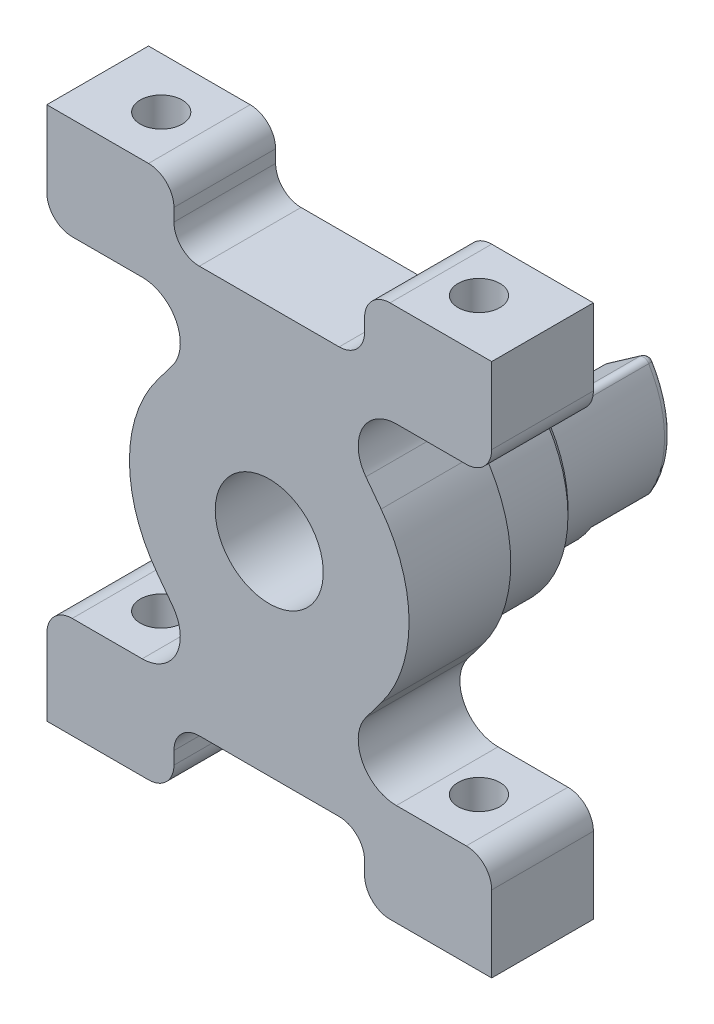
SolidWorks part; units mm, degrees
material "6061 合金"
ref_plane "前视基准面" through (0, 0, 0) normal (0, 0, 1) x (1, 0, 0)
ref_plane "上视基准面" through (0, 0, 0) normal (0, 1, 0) x (1, 0, 0)
ref_plane "右视基准面" through (0, 0, 0) normal (1, 0, 0) x (0, 0, -1)
sketch "草图1" plane through (0, 0, 0) normal (0, 0, 1) x (1, 0, 0)
  line L1 (-17.5, 21) -> (17.5, 21)
  line L2 (-17.5, 21) -> (-17.5, -21)
  line L3 (-17.5, -21) -> (17.5, -21)
  line L4 (17.5, 21) -> (17.5, -21)
  line L5 (-17.5, 21) -> (17.5, -21) construction
  line L6 (-17.5, -21) -> (17.5, 21) construction
  point P0 (0, 0)
  dimension "D1" = 35
  dimension "D2" = 42
extrude "凸台-拉伸1" add sketch "草图1" along normal mid plane 8
sketch "草图2" plane through (0, 21, 0) normal (0, 1, 0) x (1, 0, 0)
  line L0 (-12.5, 0) -> (12.5, 0) construction
  point P3 (0, 0)
  dimension "D1" = 25
sketch "草图5" plane through (0, 0, -4) normal (0, 0, -1) x (-1, 0, 0)
  circle A0 centre (0, 0) radius 8.5
  dimension "D1" = 17
extrude "凸台-拉伸2" add sketch "草图5" along normal blind 10.1
sketch "草图6" plane through (0, 0, 0) normal (0, 1, 0) x (1, 0, 0)
  line L0 (8.5, 4) -> (8.5, 14.1) construction
  line L1 (8.5, 10) -> (10, 10)
  line L2 (8.5, 10) -> (8.5, 4)
  line L3 (8.5, 4) -> (10, 4)
  line L4 (10, 10) -> (10, 4)
  line L5 (17.5, 4) -> (-17.5, 4) construction
  line L6 (0, 0) -> (0, 4) construction
  dimension "D1" = 6
  dimension "D3" = 10
revolve "旋转1" add sketch "草图6" angle 360 about L6
chamfer "倒角1" distance 0.5 angle 45 1 edges at (10, 0, -10)
sketch "草图7" plane through (0, 0, -14.1) normal (0, 0, -1) x (-1, 0, 0)
  circle A0 centre (0, 0) radius 6.5 construction
  dimension "D1" = 13
hole_wizard "M3 螺纹孔1" positions "草图8" profile "草图9" tap size "M3" standard "ISO"
sketch "草图8" plane through (0, 0, -14.1) normal (0, 0, -1) x (-1, 0, 0)
  circle A0 centre (0, 0) radius 6.5 construction
  point P0 (0, 6.5)
  point P6 (0, -6.5)
sketch "草图9" plane through (0, 6.5, -14.1) normal (1, 0, 0) x (0, 1, 0)
  line L0 (0, 0) -> (0, 10.7511)
  line L1 (0, 10.7511) -> (1.25, 10)
  line L2 (1.25, 10) -> (1.25, 0)
  line L5 (1.25, 0) -> (0, 0)
  line L10 (0, 10.7511) -> (-1.25, 10) construction
  line L11 (0, -6.35) -> (0, 107.95) construction
  dimension "螺纹孔钻头直径" = 2.5
  dimension "螺纹孔钻头深度" = 10
  dimension "导头角度" = 118
cosmetic thread "孔螺蚊线4" parameters "D1"=6, "D2"=3
cosmetic thread "孔螺蚊线6" parameters "D1"=6, "D2"=3
sketch "草图10" plane through (0, 0, -14.1) normal (0, 0, -1) x (-1, 0, 0)
  circle A0 centre (0, 0) radius 4.25
  dimension "D1" = 8.5
extrude "切除-拉伸1" cut sketch "草图10" against normal through all
sketch "草图12" plane through (0, 0, -4) normal (0, 0, -1) x (-1, 0, 0)
  line L0 (17.5, 0) -> (21, 0)
  line L1 (-17.5, 21) -> (17.5, 21)
  line L2 (-17.5, 21) -> (-17.5, -21)
  line L3 (-17.5, -21) -> (17.5, -21)
  line L4 (17.5, 21) -> (17.5, -21)
  line L5 (-17.5, 21) -> (17.5, -21) construction
  line L6 (-17.5, -21) -> (17.5, 21) construction
  line L7 (-17.5, 0) -> (-21, 0)
  line L8 (-17.5, 11.6082) -> (-13.0958, 11.6082)
  line L9 (13.0958, 11.6082) -> (17.5, 11.6082)
  line L10 (17.5, -11.6082) -> (13.0958, -11.6082)
  line L11 (-13.0958, -11.6082) -> (-17.5, -11.6082)
  circle A0 centre (0, 0) radius 17.5
  circle A1 centre (0, 0) radius 21
  dimension "D1" = 42
  dimension "D2" = 35
sketch "草图13" plane through (0, 0, -14.1) normal (0, 0, -1) x (-1, 0, 0)
  line L0 (-8.5, 0) -> (8.5, 0) construction
  line L1 (6.9628, 4.8754) -> (0, 0)
  line L2 (0, 0) -> (6.9628, -4.8754)
  circle A0 centre (0, 0) radius 4.25
  circle A1 centre (0, 0) radius 8.5
  circle A3 centre (0, 0) radius 8.5 construction
  circle M6 centre (0, 0) radius 4.25
  circle M9 centre (0, 0) radius 8.5
  dimension "D1" = 8.5
  dimension "D2" = 35
  dimension "D3" = 35
extrude "凸台-拉伸3" add sketch "草图13" along normal blind 5 contours L0 A1 L1 M6 | L0 A0 L2 M9 region at (-6.2076, 1.9572, -14.1) region at (-6.2076, -1.9572, -14.1)
mirror "镜向1" about plane through (0, 0, 0) normal (1, 0, 0) of "凸台-拉伸3"
fillet "圆角1" radius 0.5 16 edges at (-5.2221, 3.6565, -19.1) (-5.2221, -3.6565, -19.1) (-4.25, 0, -19.1) (-8.5, 0, -19.1) (5.2221, -3.6565, -19.1) (5.2221, 3.6565, -19.1) (8.5, 0, -19.1) (4.25, 0, -19.1) (3.4814, 2.4377, -16.6) (6.9628, 4.8754, -16.6) (6.9628, -4.8754, -16.6) (3.4814, -2.4377, -16.6) (-3.4814, 2.4377, -16.6) (-6.9628, 4.8754, -16.6) (-6.9628, -4.8754, -16.6) (-3.4814, -2.4377, -16.6)
sketch "草图14" plane through (0, 0, -4) normal (0, 0, -1) x (-1, 0, 0)
  line L4 (-17.5, 21) -> (-17.5, -21)
  line L5 (-17.5, -21) -> (17.5, -21)
  line L6 (17.5, -21) -> (17.5, 21)
  line L7 (17.5, 21) -> (-17.5, 21)
  line L8 (-17.5, 21) -> (-17.5, -21)
  line L9 (-17.5, -21) -> (17.5, -21)
  line L10 (17.5, -21) -> (17.5, 21)
  line L11 (17.5, 21) -> (-17.5, 21)
  line L30 (9.5, -21) -> (15.5, -21)
  line L31 (7.5, -18) -> (7.5, -19)
  line L32 (-5.5, -16) -> (5.5, -16)
  line L33 (-7.5, -19) -> (-7.5, -18)
  line L34 (-15.5, -21) -> (-9.5, -21)
  line L35 (-17.5, -15) -> (-17.5, -19)
  line L36 (-10, -13) -> (-15.5, -13)
  line L37 (-8.8, -6.6) -> (-7.6, -8.2)
  line L38 (7.6, -8.2) -> (8.8, -6.6)
  line L39 (15.5, -13) -> (10, -13)
  line L40 (17.5, -19) -> (17.5, -15)
  line L41 (-17.5, -21) -> (-17.5, 21) construction
  line L42 (17.5, -21) -> (-17.5, -21) construction
  line L52 (-9.5, 21) -> (-15.5, 21)
  line L53 (-7.5, 18) -> (-7.5, 19)
  line L54 (5.5, 16) -> (-5.5, 16)
  line L55 (7.5, 19) -> (7.5, 18)
  line L56 (15.5, 21) -> (9.5, 21)
  line L57 (17.5, 15) -> (17.5, 19)
  line L58 (10, 13) -> (15.5, 13)
  line L59 (8.8, 6.6) -> (7.6, 8.2)
  line L60 (-7.6, 8.2) -> (-8.8, 6.6)
  line L61 (-15.5, 13) -> (-10, 13)
  line L62 (-17.5, 19) -> (-17.5, 15)
  arc A22 (7.5, -19) -> (9.5, -21) centre (9.5, -19) ccw
  arc A23 (7.5, -18) -> (5.5, -16) centre (5.5, -18) ccw
  arc A24 (-5.5, -16) -> (-7.5, -18) centre (-5.5, -18) ccw
  arc A25 (-9.5, -21) -> (-7.5, -19) centre (-9.5, -19) ccw
  arc A26 (-17.5, -19) -> (-15.5, -21) centre (-15.5, -19) ccw
  arc A27 (-15.5, -13) -> (-17.5, -15) centre (-15.5, -15) ccw
  arc A28 (-10, -13) -> (-7.6, -8.2) centre (-10, -10) ccw
  arc A29 (-8.8, -6.6) -> (8.8, -6.6) centre (0, 0) ccw
  arc A30 (7.6, -8.2) -> (10, -13) centre (10, -10) ccw
  arc A31 (17.5, -15) -> (15.5, -13) centre (15.5, -15) ccw
  arc A32 (15.5, -21) -> (17.5, -19) centre (15.5, -19) ccw
  arc A35 (-8.8, 6.6) -> (-8.8, -6.6) centre (0, 0) ccw
  arc A36 (8.8, -6.6) -> (8.8, 6.6) centre (0, 0) ccw
  arc A44 (-7.5, 19) -> (-9.5, 21) centre (-9.5, 19) ccw
  arc A45 (-7.5, 18) -> (-5.5, 16) centre (-5.5, 18) ccw
  arc A46 (5.5, 16) -> (7.5, 18) centre (5.5, 18) ccw
  arc A47 (9.5, 21) -> (7.5, 19) centre (9.5, 19) ccw
  arc A48 (17.5, 19) -> (15.5, 21) centre (15.5, 19) ccw
  arc A49 (15.5, 13) -> (17.5, 15) centre (15.5, 15) ccw
  arc A50 (10, 13) -> (7.6, 8.2) centre (10, 10) ccw
  arc A51 (8.8, 6.6) -> (-8.8, 6.6) centre (0, 0) ccw
  arc A52 (-7.6, 8.2) -> (-10, 13) centre (-10, 10) ccw
  arc A53 (-17.5, 15) -> (-15.5, 13) centre (-15.5, 15) ccw
  arc A54 (-15.5, 21) -> (-17.5, 19) centre (-15.5, 19) ccw
  line M50 (-17.5, 21) -> (-17.5, -21)
  line M51 (-17.5, -21) -> (17.5, -21)
  line M52 (17.5, -21) -> (17.5, 21)
  line M53 (17.5, 21) -> (-17.5, 21)
  dimension "D2" = 2
  dimension "D3" = 3
  dimension "D4" = 11
  dimension "D5" = 7.5
  dimension "D6" = 8.7
  dimension "D7" = 10
  dimension "D8" = 5
  dimension "D1" = 0
extrude "切除-拉伸2" cut sketch "草图14" against normal through all contours L58 A50 L59 A36 L38 A30 L39 A31 A49 M52 | A53 A27 L36 A28 L37 A35 L60 A52 L61 M50 | A25 A22 L31 A23 L32 A24 L33 M51 | A47 A44 L53 A45 L54 A46 L55 M53 region at (13.1528, 0, -4) region at (0, 18.594, -4) region at (0, -18.594, -4) region at (-13.1528, 0, -4)
hole_wizard "M4 螺纹孔1" positions "草图3" profile "草图4" tap size "M4" standard "ISO" end condition up to next
sketch "草图3" plane through (0, 21, 0) normal (0, 1, 0) x (1, 0, 0)
  point P0 (-12.5, 0)
  point P3 (12.5, 0)
sketch "草图4" plane through (-12.5, 21, 0) normal (1, 0, 0) x (0, 0, 1)
  line L0 (0, 0) -> (0, 8)
  line L1 (0, 8) -> (1.65, 8)
  line L2 (1.65, 8) -> (1.65, 0)
  line L5 (1.65, 0) -> (0, 0)
  line L11 (0, -6.35) -> (0, 107.95) construction
  dimension "通孔螺纹孔钻头直径" = 3.3
  dimension "通孔螺纹孔钻头深度" = 8
cosmetic thread "孔螺蚊线1" parameters "D2"=4
cosmetic thread "孔螺蚊线2" parameters "D2"=4
mirror "镜向2" about plane through (0, 0, 0) normal (0, 1, 0) of "M4 螺纹孔1"
cosmetic thread "孔螺蚊线7" parameters "D2"=4
cosmetic thread "孔螺蚊线8" parameters "D2"=4
